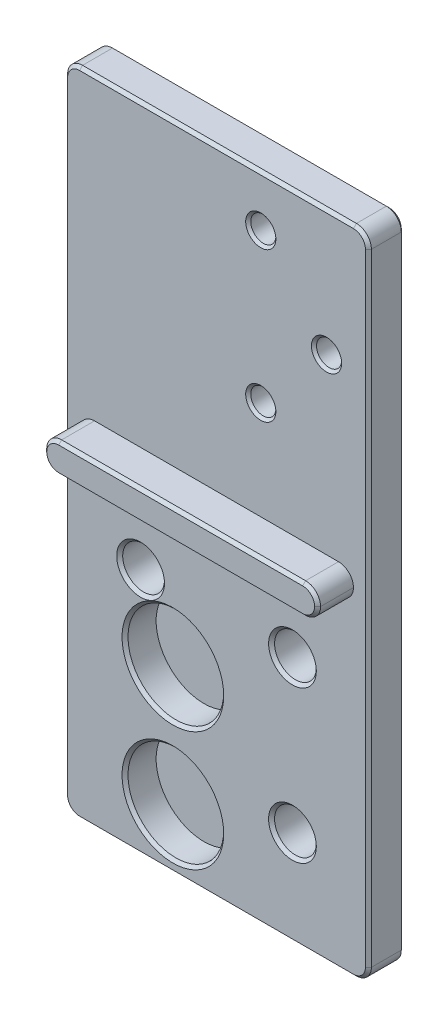
SolidWorks part; units mm, degrees
note: The reader was unsure of these and kept them because the rebuilt part matched: shared geometry of "Sketch1<5>", "Sketch1<4>".
ref_plane "Front Plane" through (0, 0, 0) normal (0, 0, 1) x (1, 0, 0)
ref_plane "Top Plane" through (0, 0, 0) normal (0, 1, 0) x (1, 0, 0)
ref_plane "Right Plane" through (0, 0, 0) normal (1, 0, 0) x (0, 0, -1)
sketch "main_features_sketch" plane through (0, 0, 0) normal (0, 0, 1) x (1, 0, 0)
  line L0 (-25.4, 0) -> (25.4, 0) construction
  line L1 (-25.4, 25) -> (25.4, 25)
  line L2 (-25.4, 25) -> (-25.4, -25)
  line L3 (-25.4, -25) -> (25.4, -25)
  line L4 (25.4, 25) -> (25.4, -25)
  line L5 (-25.4, 25) -> (25.4, -25) construction
  line L6 (-25.4, -25) -> (25.4, 25) construction
  line L7 (7.4, 16.5) -> (7.4, -8.5) construction
  line L8 (-25.4, -25) -> (-25.4, -84)
  line L9 (25.4, -30) -> (-25.4, -30)
  line L10 (25.4, -84) -> (25.4, -25)
  line L11 (-12.7, -42.7) -> (-25.4, -42.7) construction
  line L12 (18.4, 4) -> (7.4, 4) construction
  line L13 (-12.7, -42.7) -> (-12.7, -30) construction
  line L14 (-12.7, -42.7) -> (0, -42.7) construction
  line L15 (0, -42.7) -> (12.7, -42.7) construction
  line L16 (-22.9, -25) -> (-22.9, -30)
  line L17 (25.4, -84) -> (-25.4, -84)
  line L18 (22.9, -25) -> (22.9, -30)
  line L19 (12.7, -42.7) -> (12.7, -55.4) construction
  line L20 (12.7, -55.4) -> (12.7, -68.1) construction
  line L21 (22.9, -27.5) -> (25.4, -27.5) construction
  line L22 (-22.9, -27.5) -> (-25.4, -27.5) construction
  circle A0 centre (18.4, 4) radius 2.1
  circle A1 centre (7.4, -8.5) radius 2.1
  circle A2 centre (7.4, 16.5) radius 2.1
  circle A3 centre (-12.7, -42.7) radius 3.4925
  circle A5 centre (12.7, -42.7) radius 3.4925
  circle A6 centre (-7.3, -54) radius 8
  circle A7 centre (-7.3, -74) radius 8
  circle A8 centre (12.7, -68.1) radius 3.4925
  arc A9 (-6.3515, -77.123) -> (-6.3515, -70.877) centre (-7.3, -74) ccw construction
  point P0 (0, 0)
  point P13 (7.4, 4)
  dimension "D3" = 4.2
  dimension "D7" = 6.985
  dimension "D9" = 16
  dimension "D1" = 50
  dimension "D2" = 25
  dimension "D4" = 11
  dimension "D5" = 7
  dimension "D6" = 50.8
  dimension "D8" = 12.7
  dimension "D10" = 2
  dimension "D11" = 5
  dimension "D12" = 4
  dimension "D13" = 2.5
extrude "main_body" add sketch "main_features_sketch" along normal blind 6
extrude "ledge" add sketch "Sketch1<5>" along normal blind 12 contours L9 L10 L3 L8
sketch "Sketch1<5>" plane through (0, 0, 0) normal (0, 0, 1) x (1, 0, 0) same geometry as "main_features_sketch"
extrude "screw_head_recesses" add sketch "Sketch1<4>" along normal offset from surface (0.8 mm away) 5.2 contours L17 A7 | A6
sketch "Sketch1<4>" plane through (0, 0, 0) normal (0, 0, 1) x (1, 0, 0) same geometry as "main_features_sketch"
hole_wizard "M5x0.8 Tapped Hole1" positions "Sketch2" profile "Sketch3" tap size "M5x0.8" standard "ANSI Metric" end condition through all
sketch "Sketch2" plane through (0, 0, 6) normal (0, 0, 1) x (1, 0, 0)
  point P0 (7.4, -8.5)
  point P3 (7.4, 16.5)
  point P6 (18.4, 4)
  point P12 (0, 0)
  point P13 (7.4, 16.5)
  point P15 (7.4, -8.5)
  point P17 (18.6664, 3.1137)
  point P18 (18.4, 4)
sketch "Sketch3" plane through (7.4, -8.5, 6) normal (1, 0, 0) x (0, -1, 0)
  line L0 (0, 0) -> (0, 6)
  line L1 (0, 6) -> (2.525, 6)
  line L2 (2.1, 5.575) -> (2.1, 0.425)
  line L3 (2.1, 0.425) -> (2.525, 0)
  line L5 (2.525, 0) -> (0, 0)
  line L6 (-2.1, 0.425) -> (-2.525, 0) construction
  line L7 (2.525, 6) -> (2.1, 5.575)
  line L8 (-2.525, 6) -> (-2.1, 5.575) construction
  line L11 (0, -6.35) -> (0, 107.95) construction
  dimension "Thru Tap Drill Dia." = 4.2
  dimension "Thru Tap Drill Depth" = 6
  dimension "Near C'Sink Dia." = 5.05
  dimension "Near C'Sink Angle" = 90
  dimension "Far C'Sink Dia." = 5.05
  dimension "Far C'Sink Angle" = 90
cosmetic thread "Hole Thread1" parameters "D2"=5
cosmetic thread "Hole Thread2" parameters "D2"=5
cosmetic thread "Hole Thread3" parameters "D2"=5
fillet "Fillet1" radius 2.5 8 edges at (25.4, 25, 3) (-25.4, 25, 3) (25.4, -84, 3) (-25.4, -84, 3) (22.9, -25, 9) (22.9, -30, 9) (-22.9, -25, 9) (-22.9, -30, 9)
chamfer "Chamfer1" distance 0.5 angle 45 30 edges at (-9.2075, -42.7, 0) (16.1925, -42.7, 0) (-24.6678, 24.2678, 0) (-25.4, -29.5, 0) (25.4, -29.5, 0) (24.6678, 24.2678, 0) (0, 25, 0) (-9.2075, -42.7, 6) (16.1925, -42.7, 6) (-25.4, -29.5, 6) (-24.6678, 24.2678, 6) (0, 25, 6) (24.6678, 24.2678, 6) (25.4, -29.5, 6) (16.1925, -68.1, 0) (0, -84, 0) (0.7, -54, 6) (16.1925, -68.1, 6) (0, -84, 6) (0.7, -74, 6) (-24.6678, -83.2678, 0) (24.6678, -83.2678, 0) (-24.6678, -83.2678, 6) (24.6678, -83.2678, 6) (0, -25, 12) (0, -30, 12) (22.1678, -25.7322, 12) (-22.1678, -25.7322, 12) (22.1678, -29.2678, 12) (-22.1678, -29.2678, 12)
